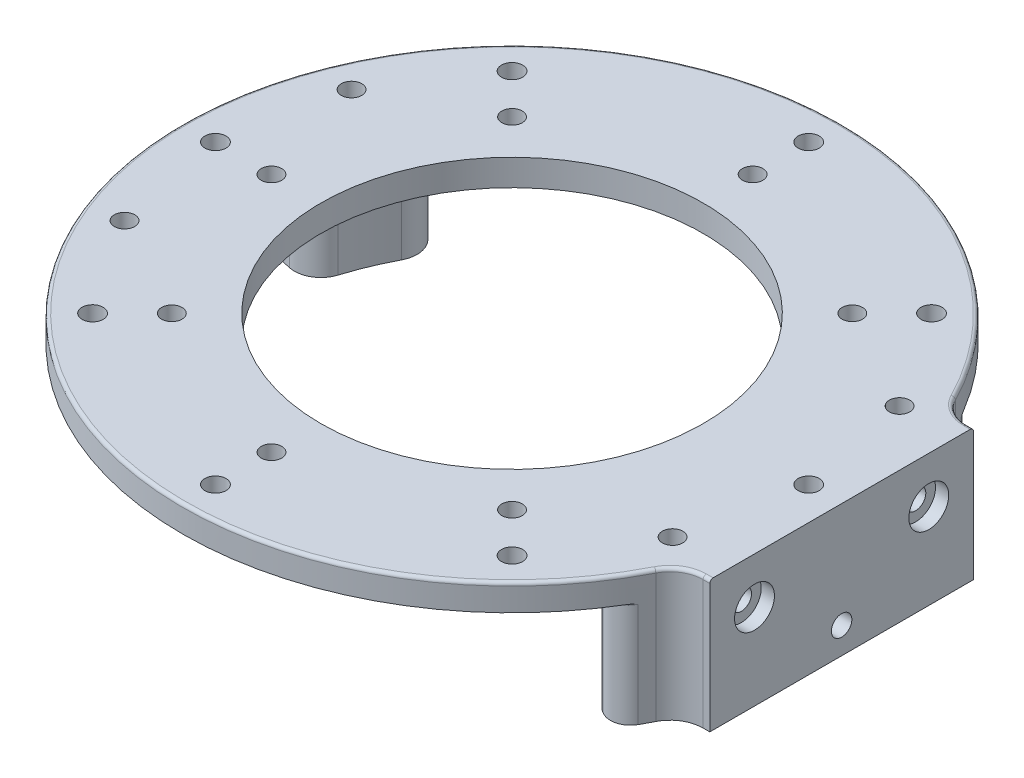
SolidWorks part; units mm, degrees
material "6061 合金"
ref_plane "前视基准面" through (0, 0, 0) normal (0, 0, 1) x (1, 0, 0)
ref_plane "上视基准面" through (0, 0, 0) normal (0, 1, 0) x (1, 0, 0)
ref_plane "右视基准面" through (0, 0, 0) normal (1, 0, 0) x (0, 0, -1)
sketch "草图1" plane through (0, 0, 0) normal (0, 1, 0) x (1, 0, 0)
  circle A0 centre (0, 0) radius 50
  dimension "D1" = 100
extrude "凸台-拉伸1" add sketch "草图1" along normal mid plane 40
sketch "草图2" plane through (0, 20, 0) normal (0, 1, 0) x (1, 0, 0)
  circle A0 centre (0, 0) radius 29
  dimension "D1" = 58
extrude "切除-拉伸1" cut sketch "草图2" against normal up to next
sketch "草图3" plane through (0, 20, 0) normal (0, 1, 0) x (1, 0, 0)
  circle A0 centre (0, 45) radius 1.6
  dimension "D2" = 3.2
  dimension "D1" = 45
extrude "切除-拉伸2" cut sketch "草图3" against normal up to next
pattern_circular "阵列(圆周)1" count 8 over 360 about axis through (0, 20, 0) along (0, 1, 0) of "切除-拉伸2"
sketch "草图4" plane through (0, 20, 0) normal (0, 1, 0) x (1, 0, 0)
  circle A0 centre (0, 36.5) radius 1.55
  dimension "D2" = 3.1
  dimension "D1" = 36.5
extrude "切除-拉伸3" cut sketch "草图4" against normal up to next
pattern_circular "阵列(圆周)2" count 8 over 360 about axis through (0, 20, 0) along (0, 1, 0) of "切除-拉伸3"
sketch "草图5" plane through (0, -20, 0) normal (0, -1, 0) x (1, 0, 0)
  circle A0 centre (0, 0) radius 40
  dimension "D1" = 80
extrude "切除-拉伸4" cut sketch "草图5" against normal offset from surface (36 mm away) 4 up to face at (-34.95, 20, 0)
sketch "草图6" plane through (0, 0, 0) normal (0, 1, 0) x (1, 0, 0)
  line L0 (0, 0) -> (-80.7225, 0) construction
  line L1 (-39.1259, -8.3165) -> (-48.9074, -10.3956)
  line L2 (-39.1259, 8.3165) -> (-48.9074, 10.3956)
  circle A0 centre (0, 0) radius 50 construction
  circle A1 centre (0, 0) radius 40 construction
  arc A2 (-48.9074, 10.3956) -> (-48.9074, -10.3956) centre (0, 0) ccw
  arc A3 (-39.1259, 8.3165) -> (-39.1259, -8.3165) centre (0, 0) ccw
  dimension "D1" = 24
  dimension "D2" = 12
extrude "切除-拉伸6" cut sketch "草图6" against normal mid plane 32
pattern_circular "阵列(圆周)3" count 8 over 360 about axis through (0, -20.001, 0) along (0, 1, 0) skipping 2, 4 of "切除-拉伸6"
ref_plane "基准面1" through (50, 0, 0) normal (1, 0, 0) x (0, 0, -1)
sketch "草图10" plane through (50, 0, 0) normal (1, 0, 0) x (0, 0, -1)
  line L0 (-50, -20) -> (50, -20) construction
  line L1 (-20, 20) -> (20, 20)
  line L2 (-20, 20) -> (-20, -20)
  line L3 (-20, -20) -> (20, -20)
  line L4 (20, 20) -> (20, -20)
  line L5 (-20, 20) -> (20, -20) construction
  line L6 (-20, -20) -> (20, 20) construction
  point P0 (0, 0)
  dimension "D1" = 40
extrude "凸台-拉伸5" add sketch "草图10" against normal up to surface (4.1742 mm away) up to face at (34.969, 0, -34.969)
ref_plane "基准面2" through (70, 0, 0) normal (1, 0, 0) x (0, 0, -1)
sketch "草图14" plane through (0, 0, 0) normal (0, 1, 0) x (1, 0, 0)
  line L0 (45, 0) -> (-45, 0) construction
  line L1 (-27.232, -41.9335) -> (-21.7856, -33.5468) construction
  line L2 (-27.232, 41.9335) -> (-21.7856, 33.5468)
  line L3 (41.9335, 27.232) -> (33.5468, 21.7856)
  line L5 (-27.232, -41.9335) -> (-21.7856, -33.5468)
  line L6 (41.9335, -27.232) -> (33.5468, -21.7856)
  line L8 (41.9335, -27.232) -> (33.5468, -21.7856) construction
  arc A0 (-21.7856, 33.5468) -> (33.5468, 21.7856) centre (0, 0) cw
  arc A1 (45.8258, 20) -> (45.8258, -20) centre (0, 0) ccw construction
  arc A2 (-27.232, 41.9335) -> (41.9335, 27.232) centre (0, 0) cw
  circle A3 centre (0, 0) radius 40 construction
  arc A4 (-27.232, -41.9335) -> (41.9335, -27.232) centre (0, 0) ccw
  arc A5 (-21.7856, -33.5468) -> (33.5468, -21.7856) centre (0, 0) ccw
extrude "切除-拉伸8" cut sketch "草图14" against normal up to surface (16 mm away) and the other way up to surface (16 mm away) up to face at (-31.4721, -16, -31.4721) other way up to face at (0, 16, -34.95)
sketch "草图15" plane through (0, -20, 0) normal (0, -1, 0) x (1, 0, 0)
  line L0 (0, 0) -> (-45, 0) construction
  line L1 (0, 0) -> (-31.8198, 31.8198) construction
  line L2 (0, 0) -> (-46.194, 19.1342) construction
  line L3 (0, 0) -> (0, -29) construction
  arc A0 (45.8258, 20) -> (45.8258, -20) centre (0, 0) ccw construction
  circle A1 centre (0, 0) radius 45 construction
  circle A2 centre (-41.5746, 17.2208) radius 1.55
  circle A3 centre (-41.5746, -17.2208) radius 1.55
  circle A4 centre (0, 0) radius 29 construction
  circle A5 centre (41.5746, -17.2208) radius 1.55
  circle A6 centre (41.5746, 17.2208) radius 1.55
  dimension "D2" = 3.1
  dimension "D1" = 22.5
extrude "切除-拉伸10" cut sketch "草图15" against normal through all
ref_plane "基准面3" through (43.5, 0, 0) normal (1, 0, 0) x (0, 0, -1)
sketch "草图36" plane through (0, -20, 0) normal (0, -1, 0) x (1, 0, 0)
  circle A0 centre (-41.5746, 17.2208) radius 3.5
  circle A1 centre (-41.5746, -17.2208) radius 3.5
  circle A2 centre (41.5746, 17.2208) radius 3.5
  circle A3 centre (41.5746, -17.2208) radius 3.5
  dimension "D1" = 7
  dimension "D2" = 7
  dimension "D3" = 7
  dimension "D4" = 7
extrude "切除-拉伸23" cut sketch "草图36" against normal blind 5
fillet "圆角4" radius 4 8 edges at (-41.9335, 0, -27.232) (-33.5468, 0, -21.7856) (-39.1259, 0, -8.3165) (-48.9074, 0, -10.3956) (-39.1259, 0, 8.3165) (-48.9074, 0, 10.3956) (-33.5468, 0, 21.7856) (-41.9335, 0, 27.232)
sketch "草图38" plane through (0, -20, 0) normal (0, -1, 0) x (1, 0, 0)
  line L1 (-57.2717, 62.1415) -> (98.5037, 62.1415)
  line L2 (-57.2717, 62.1415) -> (-57.2717, -59.6108)
  line L3 (-57.2717, -59.6108) -> (98.5037, -59.6108)
  line L4 (98.5037, 62.1415) -> (98.5037, -59.6108)
extrude "切除-拉伸25" cut sketch "草图38" against normal blind 20
sketch "草图40" plane through (0, 0, 0) normal (0, -1, 0) x (1, 0, 0)
  circle A0 centre (41.5746, 17.2208) radius 1.55
  circle A1 centre (41.5746, 17.2208) radius 3
  circle A2 centre (41.5746, -17.2208) radius 1.55
  circle A3 centre (41.5746, -17.2208) radius 3
  circle A4 centre (-41.5746, 17.2208) radius 1.55
  circle A5 centre (-41.5746, 17.2208) radius 3
  circle A6 centre (-41.5746, -17.2208) radius 1.55
  circle A7 centre (-41.5746, -17.2208) radius 3
  dimension "D1" = 6
  dimension "D2" = 6
  dimension "D3" = 6
  dimension "D4" = 6
  dimension "D5" = 3.1
  dimension "D6" = 3.1
  dimension "D7" = 3.1
  dimension "D8" = 3.1
extrude "凸台-拉伸11" add sketch "草图40" along normal blind 1.5
sketch "草图50" plane through (0, 16, 0) normal (0, -1, 0) x (1, 0, 0)
  circle A0 centre (36.5, 0) radius 1.55
extrude "凸台-拉伸12" add sketch "草图50" against normal up to surface (4 mm away) up to face at (-41.5746, 20, -15.6708)
sketch "草图51" plane through (0, 16, 0) normal (0, -1, 0) x (1, 0, 0)
  circle A0 centre (-45, 0) radius 3.5
  circle A1 centre (-36.5, 0) radius 3.5
  circle A2 centre (-31.8198, 31.8198) radius 3.5
  circle A3 centre (-25.8094, 25.8094) radius 3.5
  circle A4 centre (0, 45) radius 3.5
  circle A5 centre (0, 36.5) radius 3.5
  circle A6 centre (31.8198, 31.8198) radius 3.5
  circle A7 centre (25.8094, 25.8094) radius 3.5
  circle A10 centre (31.8198, -31.8198) radius 3.5
  circle A11 centre (25.8094, -25.8094) radius 3.5
  circle A12 centre (0, -45) radius 3.5
  circle A13 centre (0, -36.5) radius 3.5
  circle A14 centre (-31.8198, -31.8198) radius 3.5
  circle A15 centre (-25.8094, -25.8094) radius 3.5
  circle A16 centre (36.5, 0) radius 3.5 [skipped]
  circle A17 centre (45, 0) radius 3.5 [skipped]
  point P36 (0, 0)
  dimension "D1" = 7
  dimension "D2" = 7
  dimension "D3" = 8
extrude "切除-拉伸27" cut sketch "草图51" against normal blind 1
sketch "草图54" plane through (0, 0, 0) normal (0, -1, 0) x (1, 0, 0)
  line L0 (53.5243, 13.22) -> (8.7506, 13.22) construction
  line L1 (45.8258, 20) -> (50, 20) construction
  line L2 (8.7506, -13.22) -> (59.29, -13.22) construction
  line L3 (37.7522, 13.22) -> (37.7522, 27.228) construction
  line L5 (37.7522, 13.22) -> (37.7522, -13.22) construction
  line L6 (65.0831, 25.6211) -> (58.1037, 32.6005) construction
  line L7 (41.9335, 27.232) -> (33.5468, 21.7856) construction
  line L8 (37.7402, 24.5088) -> (32.3711, 24.5088)
  line L9 (37.7402, 24.5088) -> (37.7402, -26.4647)
  line L10 (37.7402, -26.4647) -> (32.3711, -26.4647)
  line L11 (32.3711, 24.5088) -> (32.3711, -26.4647)
  arc A0 (33.5468, -21.7856) -> (33.5468, 21.7856) centre (0, 0) ccw construction
  circle A1 centre (0, 0) radius 27.5
  arc A3 (33.5468, -21.7856) -> (33.5468, 21.7856) centre (0, 0) ccw construction
  dimension "D4" = 55
  dimension "D1" = 6.78
extrude "切除-拉伸29" cut sketch "草图54" against normal up to surface (16 mm away) up to face at (-31.8198, 16, -35.3198)
sketch "草图55" plane through (0, 0, 0) normal (0, -1, 0) x (1, 0, 0)
  line L0 (37.7402, 13.2544) -> (37.7402, -13.2544)
  arc A0 (37.7402, -13.2544) -> (37.7402, 13.2544) centre (0, 0) ccw construction
  arc A1 (37.7402, -13.2544) -> (37.7402, 13.2544) centre (0, 0) ccw
extrude "凸台-拉伸13" add sketch "草图55" against normal up to surface (16 mm away) up to face at (-19.2818, 16, 0)
fillet "圆角9" radius 5 2 edges at (45.8258, 10, -20) (45.8258, 10, 20)
fillet "圆角10" radius 3 4 edges at (41.9335, 8, -27.232) (37.7402, 8, -24.5088) (41.9335, 8, 27.232) (37.7402, 8, 24.5088)
chamfer "倒角1" distance 3 angle 45 14 edges at (-47.439, 16, -11.4098) (-41.6124, 16, -25.4765) (-43.8423, 16, -9.319) (-37.5907, 16, -24.4117) (-40.005, 16, -9.5725) (-35.0566, 16, -21.519) (-36.9552, 16, -15.3073) (-41.6124, 16, 25.4765) (-47.439, 16, 11.4098) (-37.5907, 16, 24.4117) (-43.8423, 16, 9.319) (-35.0566, 16, 21.519) (-40.005, 16, 9.5725) (-36.9552, 16, 15.3073)
fillet "圆角11" radius 0.5 5 edges at (49.4949, 20, -20) (49.4949, 20, 20) (46.3786, 20, -20.736) (46.3786, 20, 20.736) (-50, 20, 0)
fillet "圆角12" radius 0.2 7 edges at (41.6882, 16, -25.9429) (39.2217, 16, -25.4709) (38.1037, 16, -24.3114) (41.6882, 16, 25.9429) (39.2217, 16, 25.4709) (38.1037, 16, 24.3114) (37.7402, 16, 0)
sketch "草图56" plane through (50, 0, 0) normal (1, 0, 0) x (0, 0, -1)
  line L0 (19.5, 20) -> (-19.5, 20) construction
  line L1 (-20, 19.5) -> (-20, 0) construction
  line L2 (20, 0) -> (20, 19.5) construction
  circle A0 centre (-13.22, 13) radius 1.55
  circle A1 centre (13.22, 13) radius 1.55
  circle A2 centre (0, 4) radius 1.55
  dimension "D2" = 6.78
  dimension "D4" = 6.78
  dimension "D5" = 3.1
  dimension "D6" = 3.1
  dimension "D7" = 4
  dimension "D8" = 3.1
  dimension "D1" = 7
  dimension "D3" = 7
extrude "切除-拉伸30" cut sketch "草图56" against normal up to surface (12.2598 mm away) up to face at (37.7402, 7.9, 0)
sketch "草图57" plane through (50, 0, 0) normal (1, 0, 0) x (0, 0, -1)
  circle A0 centre (13.22, 13) radius 3.025
  circle A1 centre (-13.22, 13) radius 3.025
  dimension "D1" = 6.05
  dimension "D2" = 6.05
extrude "切除-拉伸31" cut sketch "草图57" against normal blind 2
